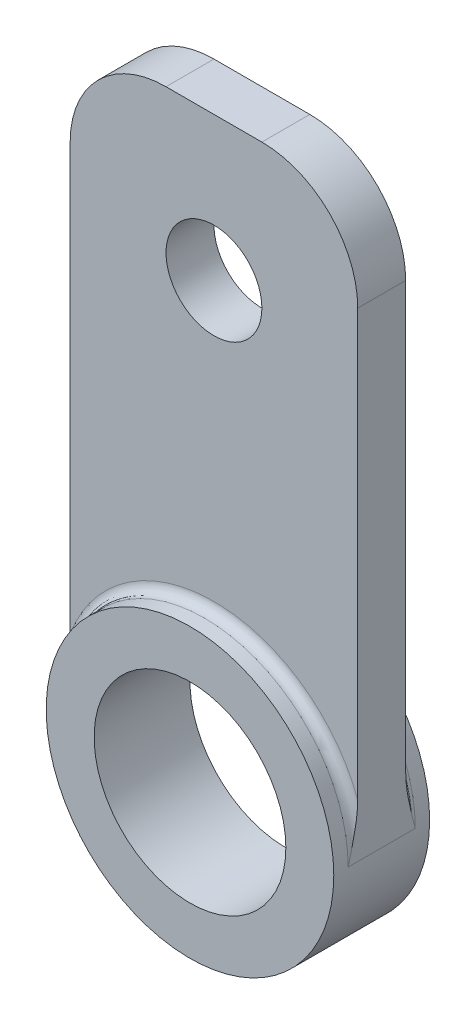
SolidWorks part; units mm, degrees
ref_plane "Front Plane" through (0, 0, 0) normal (0, 0, 1) x (1, 0, 0)
ref_plane "Top Plane" through (0, 0, 0) normal (0, 1, 0) x (1, 0, 0)
ref_plane "Right Plane" through (0, 0, 0) normal (1, 0, 0) x (0, 0, -1)
sketch "Sketch1" plane through (0, 0, 0) normal (0, 0, 1) x (1, 0, 0)
  circle A0 centre (0, 0) radius 10
  circle A1 centre (0, 0) radius 15
  dimension "D1" = 30
  dimension "D2" = 20
extrude "Boss-Extrude1" add sketch "Sketch1" along normal mid plane 10
sketch "Sketch2" plane through (0, 0, 0) normal (0, 0, 1) x (1, 0, 0)
  line L2 (-15, 0) -> (-15, 50)
  line L3 (-5, 60) -> (5, 60)
  line L4 (15, 0) -> (15, 50)
  circle A0 centre (0, 0) radius 15
  circle A1 centre (0, 45) radius 5
  arc A2 (5, 60) -> (15, 50) centre (5, 50) cw
  arc A3 (-15, 50) -> (-5, 60) centre (-5, 50) cw
  point P9 (0, 0)
  point P12 (15, 60)
  point P15 (-15, 60)
  point P16 (0, 0)
  dimension "D1" = 45
  dimension "D3" = 10
  dimension "D4" = 10
  dimension "D5" = 15
  dimension "D2" = 30
  dimension "D6" = 60
extrude "Boss-Extrude2" add sketch "Sketch2" along normal mid plane 5 contours A3 L2 A0 L4 A2 L3 A1 region at (0, 34.5151, 0)
fillet "Fillet1" radius 1 2 edges at (0, 15, -2.5) (0, 15, 2.5)
